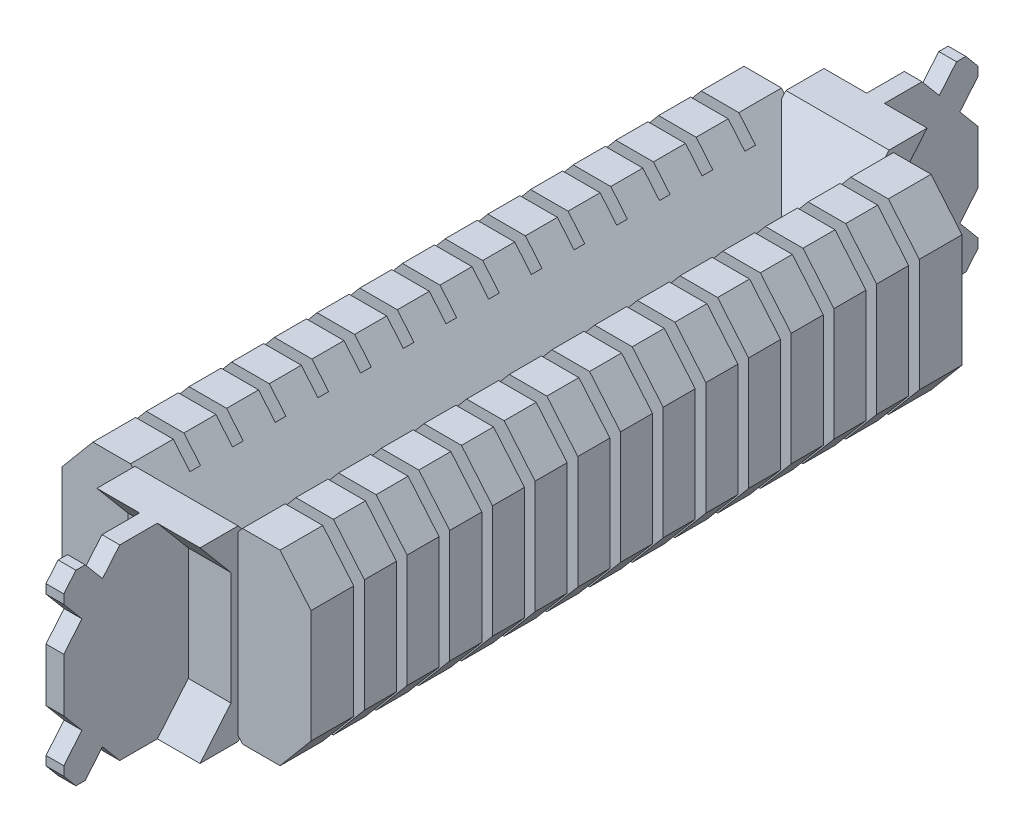
SolidWorks part; units mm, degrees
ref_plane "Ebene vorne" through (0, 0, 0) normal (0, 0, 1) x (1, 0, 0)
ref_plane "Ebene oben" through (0, 0, 0) normal (0, 1, 0) x (1, 0, 0)
ref_plane "Ebene rechts" through (0, 0, 0) normal (1, 0, 0) x (0, 0, -1)
sketch "Skizze3" plane through (0, 0, 0) normal (0, 0, 1) x (1, 0, 0)
  line L0 (-7.7197, 0) -> (0, 9.2) construction
  line L1 (0, 9.2) -> (0, -9.2) construction
  line L2 (0, -9.2) -> (-7.7197, 0) construction
  line L3 (-7.5, 0) -> (49992.5, 0) construction
  line L4 (-9, -3) -> (-9, 3) construction
  line L5 (-9, 3) -> (-2.7068, 10.5)
  line L6 (-2.7068, 10.5) -> (1.52, 10.5)
  line L7 (1.52, 10.5) -> (5, 6.3527)
  line L12 (-9, -3) -> (-15.2932, -10.5)
  line L13 (0, 9.2) -> (3, 5.6247) construction
  line L14 (3, 5.6247) -> (3, -5.6247) construction
  line L15 (3, -5.6247) -> (0, -9.2) construction
  line L16 (5, 6.3527) -> (5, -6.3527)
  line L17 (-9, -3) -> (-2.7068, -10.5)
  line L18 (-2.7068, -10.5) -> (1.52, -10.5)
  line L19 (1.52, -10.5) -> (5, -6.3527)
  line L20 (-15.2932, -10.5) -> (-19.52, -10.5)
  line L21 (-19.52, -10.5) -> (-23, -6.3527)
  line L22 (-23, 6.3527) -> (-23, -6.3527)
  line L23 (-19.52, 10.5) -> (-23, 6.3527)
  line L24 (-15.2932, 10.5) -> (-19.52, 10.5)
  line L25 (-9, 3) -> (-15.2932, 10.5)
  point P20 (-9, 0)
  point P23 (5, 0)
  point P24 (3, 3.7507)
  point P25 (-8.8519, 3.3358)
  point P26 (-9, 1.7351)
  dimension "D2" = 50
  dimension "D3" = 2
  dimension "D4" = 3
  dimension "D5" = 21
  dimension "D1" = 14
  dimension "D6" = 2
  dimension "D7" = 1.3
  dimension "D8" = 6
  dimension "D9" = 50
extrude "Aufsatz-Linear austragen2" add sketch "Skizze3" along normal mid plane 3.6
ref_plane "Ebene1" through (-9, 0, 0) normal (1, 0, 0) x (0, 0, -1)
sketch "Skizze2" plane through (0, 0, 0) normal (0, 0, 1) x (1, 0, 0)
  line L0 (-7.5519, 0) -> (0, 9)
  line L1 (0, 9) -> (0, -9) construction
  line L2 (0, -9) -> (-7.5519, 0)
  line L3 (-7.5, 0) -> (49992.5, 0) construction
  line L13 (0, 9) -> (3, 5.4247)
  line L14 (3, 5.4247) -> (3, -5.4247)
  line L15 (3, -5.4247) -> (0, -9)
  dimension "D2" = 50
  dimension "D4" = 3
  dimension "D5" = 18
  dimension "D1" = 50
extrude "Schnitt-Linear austragen1" cut sketch "Skizze2" against normal mid plane 1
mirror "Spiegeln2" about plane through (-9, 0, 0) normal (1, 0, 0) of "Schnitt-Linear austragen1"
sketch "Skizze5" plane through (0, 0, 0) normal (0, 0, 1) x (1, 0, 0)
  line L0 (-7.5519, 0) -> (-6.7163, 0.9959)
  line L1 (-6.7163, 0.9959) -> (-5.8806, 0)
  line L2 (-5.8806, 0) -> (-6.7163, -0.9959)
  line L3 (-6.7163, -0.9959) -> (-7.5519, 0)
  line L4 (-7.5519, 0) -> (49992.4481, 0) construction
  line L5 (-7.5519, 0) -> (0, -9)
  line L6 (0, -9) -> (3, -5.4247)
  line L7 (3, -5.4247) -> (3, 5.4247)
  line L8 (3, 5.4247) -> (0, 9)
  line L9 (0, 9) -> (-7.5519, 0)
  line L10 (-7.5519, 0) -> (0, -9) construction
  line L11 (0, -9) -> (3, -5.4247) construction
  line L12 (3, -5.4247) -> (3, 5.4247) construction
  line L13 (3, 5.4247) -> (0, 9) construction
  line L14 (0, 9) -> (-7.5519, 0) construction
  point P2 (-6.0094, 0)
  point P11 (-6.7374, -0.9707)
  dimension "D2" = 1.3
  dimension "D1" = 0
extrude "Schnitt-Linear austragen2" cut sketch "Skizze5" against normal through all both and the other way through all
mirror "Spiegeln3" about plane through (-9, 0, 0) normal (1, 0, 0) of "Schnitt-Linear austragen2"
sketch "Skizze6" plane through (0, 0, 1.8) normal (0, 0, 1) x (1, 0, 0)
  line L0 (0, 0) -> (50000, 0) construction
  line L2 (-2.7068, 10.5) -> (-9, 3) construction
  line L3 (-2.7068, 10.5) -> (-9, 3) construction
  line L6 (-4.5806, 8.2668) -> (-9, 3)
  line L7 (-4.5806, -8.2668) -> (-4.5806, 8.2668)
  line L11 (-4.5806, -8.2668) -> (-9, -3)
  line L13 (-9, 0) -> (-9, -50000) construction
  line L14 (-13.4194, 8.2668) -> (-9, 3)
  line L15 (-13.4194, -8.2668) -> (-13.4194, 8.2668)
  line L16 (-13.4194, -8.2668) -> (-9, -3)
  point P11 (-4.5806, 0)
  dimension "D2" = 1.3
extrude "Aufsatz-Linear austragen3" add sketch "Skizze6" along normal blind 1.2
sketch "Skizze7" plane through (0, 0, -1.8) normal (0, 0, -1) x (-1, 0, 0)
  line L4 (6.7163, -0.9959) -> (7.5519, 0)
  line L5 (7.5519, 0) -> (6.7163, 0.9959)
  line L6 (6.7163, 0.9959) -> (5.8806, 0)
  line L7 (5.8806, 0) -> (6.7163, -0.9959)
  line L8 (6.7163, -0.9959) -> (7.5519, 0)
  line L9 (7.5519, 0) -> (6.7163, 0.9959)
  line L10 (6.7163, 0.9959) -> (5.8806, 0)
  line L11 (5.8806, 0) -> (6.7163, -0.9959)
  dimension "D1" = 0
extrude "Schnitt-Linear austragen3" cut sketch "Skizze7" against normal through all
mirror "Spiegeln4" about plane through (-9, 0, 0) normal (1, 0, 0) of "Schnitt-Linear austragen3"
pattern_linear "Lineares Muster1" count 15 spacing 4.8 along (0, 0, 1) of "Aufsatz-Linear austragen2", "Schnitt-Linear austragen1", "Schnitt-Linear austragen2", "Aufsatz-Linear austragen3", "Schnitt-Linear austragen3", "Spiegeln2", "Spiegeln3", "Spiegeln4"
sketch "Skizze8" plane through (0, 0, -1.8) normal (0, 0, -1) x (-1, 0, 0)
  line L8 (2.7068, -10.5) -> (9, -3)
  line L9 (15.2932, -10.5) -> (19.52, -10.5)
  line L10 (9, 3) -> (2.7068, 10.5)
  line L11 (2.7068, 10.5) -> (-1.52, 10.5)
  line L12 (-1.52, 10.5) -> (-5, 6.3527)
  line L13 (-5, 6.3527) -> (-5, -6.3527)
  line L14 (-5, -6.3527) -> (-1.52, -10.5)
  line L15 (-1.52, -10.5) -> (2.7068, -10.5)
  line L16 (2.7068, -10.5) -> (9, -3)
  line L18 (9, 3) -> (2.7068, 10.5)
  line L19 (2.7068, 10.5) -> (-1.52, 10.5)
  line L20 (-1.52, 10.5) -> (-5, 6.3527)
  line L21 (-5, 6.3527) -> (-5, -6.3527)
  line L22 (-5, -6.3527) -> (-1.52, -10.5)
  line L23 (-1.52, -10.5) -> (2.7068, -10.5)
  line L30 (15.2932, -10.5) -> (19.52, -10.5)
  line L31 (19.52, -10.5) -> (23, -6.3527)
  line L32 (19.52, -10.5) -> (23, -6.3527)
  line L33 (23, -6.3527) -> (23, 6.3527)
  line L34 (23, -6.3527) -> (23, 6.3527)
  line L35 (23, 6.3527) -> (19.52, 10.5)
  line L36 (23, 6.3527) -> (19.52, 10.5)
  line L37 (19.52, 10.5) -> (15.2932, 10.5)
  line L38 (19.52, 10.5) -> (15.2932, 10.5)
  line L39 (15.2932, 10.5) -> (9, 3)
  line L40 (15.2932, 10.5) -> (9, 3)
  line L41 (9, -3) -> (15.2932, -10.5)
  line L42 (9, -3) -> (15.2932, -10.5)
  dimension "D1" = 0
extrude "Aufsatz-Linear austragen4" add sketch "Skizze8" along normal blind 1.2 and the other way blind 0.8
sketch "Skizze9" plane through (0, 0, 69) normal (0, 0, 1) x (1, 0, 0)
  line L32 (-2.7068, -10.5) -> (1.52, -10.5)
  line L33 (-9, -3) -> (-2.7068, -10.5)
  line L34 (-15.2932, -10.5) -> (-9, -3)
  line L35 (-19.52, -10.5) -> (-15.2932, -10.5)
  line L36 (-23, -6.3527) -> (-19.52, -10.5)
  line L37 (-23, 6.3527) -> (-23, -6.3527)
  line L38 (-19.52, 10.5) -> (-23, 6.3527)
  line L39 (-15.2932, 10.5) -> (-19.52, 10.5)
  line L40 (-9, 3) -> (-15.2932, 10.5)
  line L41 (-2.7068, 10.5) -> (-9, 3)
  line L42 (1.52, 10.5) -> (-2.7068, 10.5)
  line L43 (5, 6.3527) -> (1.52, 10.5)
  line L44 (5, -6.3527) -> (5, 6.3527)
  line L45 (1.52, -10.5) -> (5, -6.3527)
  line L46 (-2.7068, -10.5) -> (1.52, -10.5)
  line L47 (-9, -3) -> (-2.7068, -10.5)
  line L48 (-15.2932, -10.5) -> (-9, -3)
  line L49 (-19.52, -10.5) -> (-15.2932, -10.5)
  line L50 (-23, -6.3527) -> (-19.52, -10.5)
  line L51 (-23, 6.3527) -> (-23, -6.3527)
  line L52 (-19.52, 10.5) -> (-23, 6.3527)
  line L53 (-15.2932, 10.5) -> (-19.52, 10.5)
  line L54 (-9, 3) -> (-15.2932, 10.5)
  line L55 (-2.7068, 10.5) -> (-9, 3)
  line L56 (1.52, 10.5) -> (-2.7068, 10.5)
  line L57 (5, 6.3527) -> (1.52, 10.5)
  line L58 (5, -6.3527) -> (5, 6.3527)
  line L59 (1.52, -10.5) -> (5, -6.3527)
  dimension "D1" = 0
extrude "Aufsatz-Linear austragen5" add sketch "Skizze9" along normal blind 1.2 and the other way blind 0.8
sketch "Skizze10" plane through (-9, 0, 0) normal (1, 0, 0) x (0, 0, -1)
  line L0 (-1.8, 10.5) -> (3, 10.5) construction
  line L1 (-70.2, -3) -> (3, -3) construction
  line L2 (-70.2, 3) -> (3, 3) construction
  line L3 (-1.8, 10.5) -> (3, 10.5) construction
  line L4 (-70.2, -3) -> (3, -3) construction
  line L5 (-70.2, 3) -> (3, 3) construction
  line L6 (-3.2932, 3) -> (3, 10.5)
  line L7 (3, 10.5) -> (17.8, 10.5)
  line L8 (0, 0) -> (50000, 0) construction
  line L9 (-3.2932, 3) -> (3, 3)
  line L10 (3, 3) -> (3, -3)
  line L11 (17.8, 10.5) -> (17.8, -10.5)
  line L12 (3, -10.5) -> (17.8, -10.5)
  line L13 (-3.2932, -3) -> (3, -10.5)
  line L14 (-3.2932, -3) -> (3, -3)
  point P14 (17.8, 0)
  point P16 (3, 0)
  dimension "D1" = 50
  dimension "D2" = 14.8
extrude "Aufsatz-Linear austragen6" add sketch "Skizze10" along normal mid plane 2
ref_plane "Ebene2" through (0, 0, 33.6) normal (0, 0, 1) x (1, 0, 0)
mirror "Spiegeln5" about plane through (0, 0, 33.6) normal (0, 0, 1) of "Aufsatz-Linear austragen6"
sketch "Skizze12" plane through (-8, 0, 0) normal (1, 0, 0) x (0, 0, -1)
  line L0 (-2.2932, 4.1918) -> (3, 10.5)
  line L1 (3, 10.5) -> (7.28, 10.5)
  line L2 (17.8, 10.5) -> (3, 10.5) construction
  line L3 (7.28, 10.5) -> (3.8, 6.3527)
  line L4 (3.8, 6.3527) -> (3.8, -6.3527)
  line L6 (3, -4.1918) -> (3, 4.1918) construction
  line L7 (3, -4.1918) -> (3, 4.1918)
  line L8 (3, 4.1918) -> (-2.2932, 4.1918)
  line L9 (16.4, 0) -> (-49983.6, 0) construction
  line L10 (17.8, -10.5) -> (17.8, 10.5) construction
  line L11 (3, -4.1918) -> (-2.2932, -4.1918)
  line L12 (7.28, -10.5) -> (3.8, -6.3527)
  line L13 (3, -10.5) -> (7.28, -10.5)
  line L14 (-2.2932, -4.1918) -> (3, -10.5)
  line L17 (-1.8, 6.3527) -> (3, 6.3527) construction
  line L18 (-1.8, 6.3527) -> (3, 6.3527) construction
  point P18 (17.8, 0)
  point P23 (3, 0)
  point P24 (3.8, 0)
  dimension "D1" = 0.8
extrude "Aufsatz-Linear austragen7" add sketch "Skizze12" along normal blind 4.8
mirror "Spiegeln6" about plane through (0, 0, 33.6) normal (0, 0, 1) of "Aufsatz-Linear austragen7"
ref_plane "Ebene3" through (-9, 0, 0) normal (1, 0, 0) x (0, 0, -1)
mirror "Spiegeln10" about plane through (-9, 0, 0) normal (1, 0, 0) of "Aufsatz-Linear austragen7"
mirror "Spiegeln11" about plane through (0, 0, 33.6) normal (0, 0, 1) of "Spiegeln10"
sketch "Skizze16" plane through (-8, 0, 0) normal (1, 0, 0) x (0, 0, -1)
  line L0 (16.4, 0) -> (-49983.6, 0) construction
  line L1 (17.8, -10.5) -> (17.8, 10.5) construction
  line L2 (12.3702, 11.7974) -> (32151.7507, -38290.4248) construction
  line L3 (11.8914, 3.5734) -> (32151.2719, 38305.7956) construction
  line L4 (13.9623, 7.5736) -> (15.9144, 9.9) construction
  line L5 (13.9623, 7.5736) -> (15.2479, 6.0415) construction
  line L6 (15.9144, 9.9) -> (17.2, 8.3679) construction
  line L7 (15.2479, 6.0415) -> (17.2, 8.3679) construction
  line L8 (17.8, 3) -> (15.7621, 5.4286)
  line L9 (15.7621, 5.4286) -> (17.8, 7.8573)
  line L10 (17.8, 7.8573) -> (17.8, 8.8785) construction
  line L11 (17.8, 8.8785) -> (16.4394, 10.5)
  line L12 (17.8, 10.5) -> (7.28, 10.5) construction
  line L13 (16.4394, 10.5) -> (15.3894, 10.5) construction
  line L14 (15.3894, 10.5) -> (13.4481, 8.1864)
  line L15 (13.4481, 8.1864) -> (11.5068, 10.5)
  line L16 (11.5068, 10.5) -> (15.3894, 10.5)
  line L17 (16.4394, 10.5) -> (17.8, 10.5)
  line L18 (17.8, 10.5) -> (17.8, 8.8785)
  line L19 (17.8, 7.8573) -> (17.8, 3)
  line L20 (17.8, -7.8573) -> (17.8, -3)
  line L21 (17.8, -3) -> (15.7621, -5.4286)
  line L22 (15.7621, -5.4286) -> (17.8, -7.8573)
  line L23 (17.8, -10.5) -> (17.8, -8.8785)
  line L24 (16.4394, -10.5) -> (17.8, -10.5)
  line L25 (17.8, -8.8785) -> (16.4394, -10.5)
  line L26 (15.3894, -10.5) -> (13.4481, -8.1864)
  line L27 (11.5068, -10.5) -> (15.3894, -10.5)
  line L28 (13.4481, -8.1864) -> (11.5068, -10.5)
  line L29 (-33.6, 0) -> (-33.6, -50000) construction
  line L30 (-33.6, 4.51) -> (-33.6, -4.51) construction
  line L31 (-80.6481, -8.1864) -> (-78.7068, -10.5)
  line L32 (-78.7068, -10.5) -> (-82.5894, -10.5)
  line L33 (-82.5894, -10.5) -> (-80.6481, -8.1864)
  line L34 (-85, -8.8785) -> (-83.6394, -10.5)
  line L35 (-83.6394, -10.5) -> (-85, -10.5)
  line L36 (-85, -10.5) -> (-85, -8.8785)
  line L37 (-82.9621, -5.4286) -> (-85, -7.8573)
  line L38 (-85, -3) -> (-82.9621, -5.4286)
  line L39 (-85, -7.8573) -> (-85, -3)
  line L40 (-85, 7.8573) -> (-85, 3)
  line L41 (-85, 3) -> (-82.9621, 5.4286)
  line L42 (-82.9621, 5.4286) -> (-85, 7.8573)
  line L43 (-85, 10.5) -> (-85, 8.8785)
  line L44 (-83.6394, 10.5) -> (-85, 10.5)
  line L45 (-85, 8.8785) -> (-83.6394, 10.5)
  line L46 (-82.5894, 10.5) -> (-80.6481, 8.1864)
  line L47 (-78.7068, 10.5) -> (-82.5894, 10.5)
  line L48 (-80.6481, 8.1864) -> (-78.7068, 10.5)
  line L49 (17.8, -10.5) -> (17.8, 10.5) construction
  line L50 (3, 6.3527) -> (3, -6.3527) construction
  line L51 (3, 6.3527) -> (3, -6.3527) construction
  line L52 (17.8, 10.5) -> (7.28, 10.5) construction
  line L53 (15.9144, 9.9) -> (15.4002, 10.5128) construction
  line L54 (16.5572, 9.134) -> (17.0714, 9.7468) construction
  line L55 (15.9144, 9.9) -> (16.4287, 10.5128) construction
  point P4 (17.8, 0)
  point P12 (15.7473, 10.3)
  point P58 (0, 0)
  point P63 (14.9384, 8.7368)
  point P66 (14.5305, 10.3)
  point P67 (0, 0)
  dimension "D1" = 50
  dimension "D2" = 2
  dimension "D3" = 0.6
  dimension "D4" = 0.6
  dimension "D5" = 0.8
  dimension "D6" = 6
  dimension "D7" = 50
  dimension "D8" = 0.8
extrude "Schnitt-Linear austragen6" cut sketch "Skizze16" against normal through all
